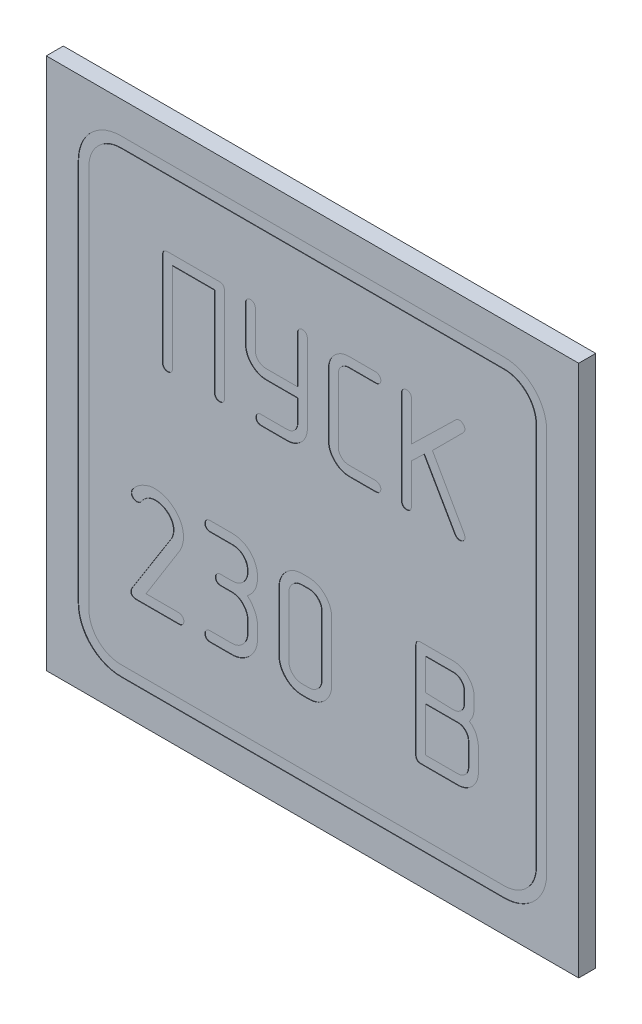
SolidWorks part; units mm, degrees
ref_plane "Спереди" through (0, 0, 0) normal (0, 0, 1) x (1, 0, 0)
ref_plane "Сверху" through (0, 0, 0) normal (0, 1, 0) x (1, 0, 0)
ref_plane "Справа" through (0, 0, 0) normal (1, 0, 0) x (0, 0, -1)
sketch "Эскиз1" plane through (0, 0, 0) normal (0, 0, 1) x (1, 0, 0)
  line L1 (0, 0) -> (25, 0)
  line L2 (0, 0) -> (0, 25)
  line L3 (0, 25) -> (25, 25)
  line L4 (25, 0) -> (25, 25)
  dimension "D1" = 25
  dimension "D2" = 25
extrude "Вытянуть1" add sketch "Эскиз1" along normal blind 0.8
sketch "Эскиз2" plane through (0, 0, 0.8) normal (0, 0, 1) x (1, 0, 0)
  line L0 (0, 0) -> (25, 0) construction
  line L1 (0, 25) -> (0, 0) construction
  text T0 "ПУСК" font "GOST type B" height 5
  text T1 "230 В" font "GOST type B" height 5
  dimension "D1" = 15
  dimension "D2" = 5
  dimension "D3" = 5
  dimension "D4" = 3.5
extrude "Вырез-Вытянуть1" cut sketch "Эскиз2" against normal blind 0.02
sketch "Эскиз3" plane through (0, 0, 0.8) normal (0, 0, 1) x (1, 0, 0)
  line L0 (25, 25) -> (0, 25) construction
  line L1 (3.5, 2) -> (21.5, 2)
  line L2 (2, 3.5) -> (2, 21.5)
  line L3 (3.5, 23) -> (21.5, 23)
  line L4 (23, 3.5) -> (23, 21.5)
  line L5 (0, 25) -> (0, 0) construction
  line L6 (25, 0) -> (25, 25) construction
  line L7 (0, 0) -> (25, 0) construction
  arc A0 (2, 21.5) -> (3.5, 23) centre (3.5, 21.5) cw
  arc A1 (21.5, 23) -> (23, 21.5) centre (21.5, 21.5) cw
  arc A2 (21.5, 2) -> (23, 3.5) centre (21.5, 3.5) ccw
  arc A3 (3.5, 2) -> (2, 3.5) centre (3.5, 3.5) cw
  dimension "D5" = 1.5
  dimension "D1" = 2
  dimension "D2" = 2
  dimension "D3" = 2
  dimension "D4" = 2
extrude "Вырез-Вытянуть-Тонкостенный1" cut sketch "Эскиз3" against normal blind 0.02 and the other way blind 0.02 thin thin type one direction wall 0.5
